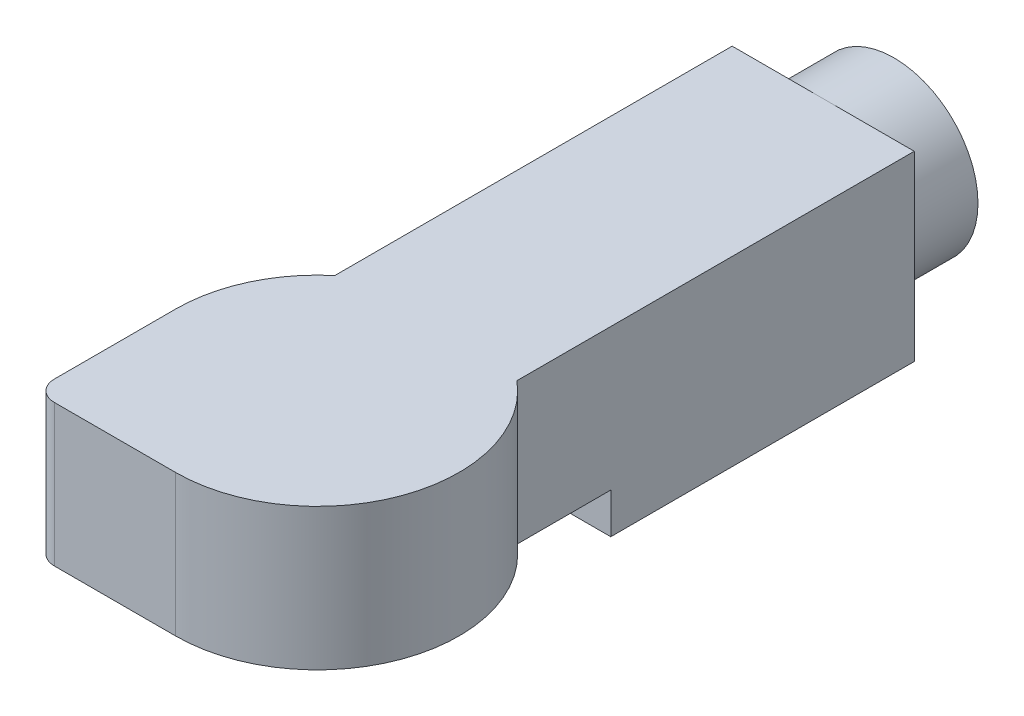
SolidWorks part; units mm, degrees
ref_plane "Front Plane" through (0, 0, 0) normal (0, 0, 1) x (1, 0, 0)
ref_plane "Top Plane" through (0, 0, 0) normal (0, 1, 0) x (1, 0, 0)
ref_plane "Right Plane" through (0, 0, 0) normal (1, 0, 0) x (0, 0, -1)
sketch "Sketch2" plane through (0, 0, 0) normal (0, 1, 0) x (1, 0, 0)
  line L1 (-45, 75) -> (45, 75)
  line L2 (-45, 75) -> (-45, -75)
  line L3 (-45, -75) -> (45, -75)
  line L4 (45, 75) -> (45, -75)
  line L5 (-45, 75) -> (45, -75) construction
  line L6 (-45, -75) -> (45, 75) construction
  point P0 (0, 0)
  dimension "D1" = 90
  dimension "D2" = 150
extrude "Boss-Extrude1" add sketch "Sketch2" along normal blind 20
sketch "Sketch3" plane through (0, 20, 0) normal (0, 1, 0) x (1, 0, 0)
  line L0 (45, -75) -> (45, 75) construction
  line L1 (-45, 75) -> (45, 75)
  line L2 (-45, 75) -> (-45, -121.381)
  line L3 (-45, -175) -> (45, -175) construction
  line L4 (45, 75) -> (45, -121.381)
  line L5 (-70, -175) -> (-70, -245)
  line L6 (-70, -245) -> (0, -245)
  line L7 (-45, -121.381) -> (-45, -175) construction
  line L8 (45, -121.381) -> (45, -175) construction
  arc A0 (0, -245) -> (45, -121.381) centre (0, -175) ccw
  arc A1 (-70, -175) -> (0, -245) centre (0, -175) ccw construction
  arc A2 (45, -121.381) -> (-45, -121.381) centre (0, -175) ccw construction
  arc A3 (-45, -121.381) -> (-70, -175) centre (0, -175) ccw
  point P7 (0, -175)
  dimension "D2" = 140
  dimension "D1" = 250
extrude "Boss-Extrude2" add sketch "Sketch3" along normal blind 70
fillet "Fillet1" radius 10 1 edges at (-70, 55, 245)
ref_axis "Path of Light" through (0, 90, 175) along (0, -1, 0)
sketch "Sketch4" plane through (0, 0, -75) normal (0, 0, -1) x (-1, 0, 0)
  line L0 (0, 90) -> (0, 20) construction
  circle A0 centre (0, 48.5) radius 41.5
  dimension "D1" = 83
extrude "Boss-Extrude3" add sketch "Sketch4" along normal blind 35
